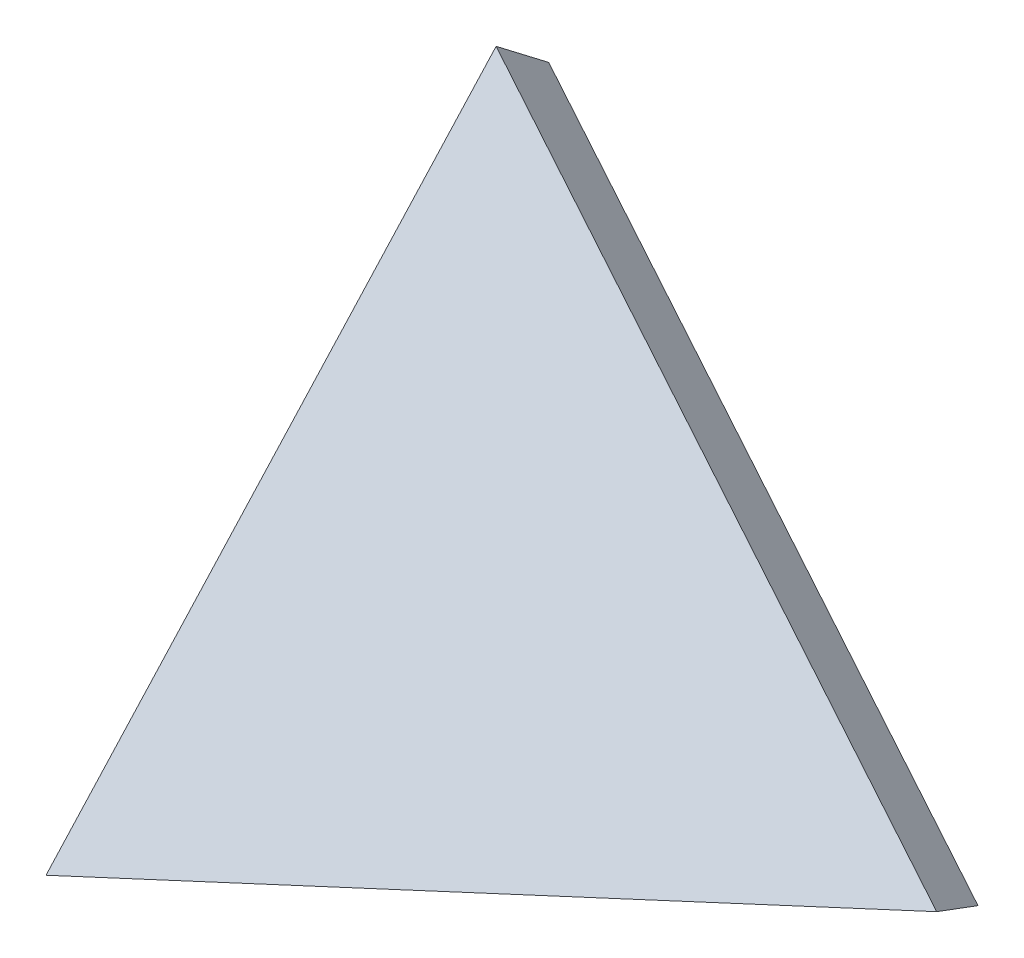
SolidWorks part; units mm, degrees
ref_plane "Front Plane" through (0, 0, 0) normal (0, 0, 1) x (1, 0, 0)
ref_plane "Top Plane" through (0, 0, 0) normal (0, 1, 0) x (1, 0, 0)
ref_plane "Right Plane" through (0, 0, 0) normal (1, 0, 0) x (0, 0, -1)
ref_plane "Plane1" through (-10.3241, -644.592, -1227.5035) normal (-0.0074, -0.4649, -0.8853) x (-1, 0.0035, 0.0066)
sketch "Sketch1" plane through (-9.8893, -592.2738, -1254.9807) normal (-0.0074, -0.4649, -0.8853) x (0.9998, -0.0173, 0.0007)
  line L0 (-1515.5225, 1908.6173) -> (-785.4595, 2356.3466)
  line L1 (-785.4595, 2356.3466) -> (-1648.3824, 2725.5982)
  line L2 (-1648.3824, 2725.5982) -> (-1515.5225, 1908.6173)
extrude "Boss-Extrude1" add sketch "Sketch1" along normal blind 70
chamfer "Chamfer1" distance 70 angle 4.62 1 edges at (-1266.9567, -2852.9679, -136.3292) first distance on face at (-1266.6961, -2836.6961, -105.3427)
chamfer "Chamfer2" distance 70 angle 5.665 1 edges at (-1627.8366, -2645.5608, -242.2084) first distance on face at (-1627.8707, -2630.7478, -210.4534)
chamfer "Chamfer3" distance 70 angle 5.44 1 edges at (-1193.8957, -2492.6643, -326.1479) first distance on face at (-1193.7558, -2476.3242, -295.1962)
equation "\"D1@Boss-Extrude1\" = \"wall_thick@4Vcorrection.Assembly\""
equation "\"A\"= \"A@4Vcorrection.Assembly\""
equation "\"Thick\"= \"wall_thick@4Vcorrection.Assembly\""
equation "\"D1@Chamfer1\"=\"Thick\""
equation "\"D2@Chamfer1\"=\"A\""
equation "\"D\"= \"D@4Vcorrection.Assembly\""
equation "\"B\"= \"B@4Vcorrection.Assembly\""
equation "\"D1@Chamfer2\"=\"Thick\""
equation "\"D2@Chamfer2\"=\"D\""
equation "\"D1@Chamfer3\"=\"Thick\""
equation "\"D2@Chamfer3\"=\"B\""
